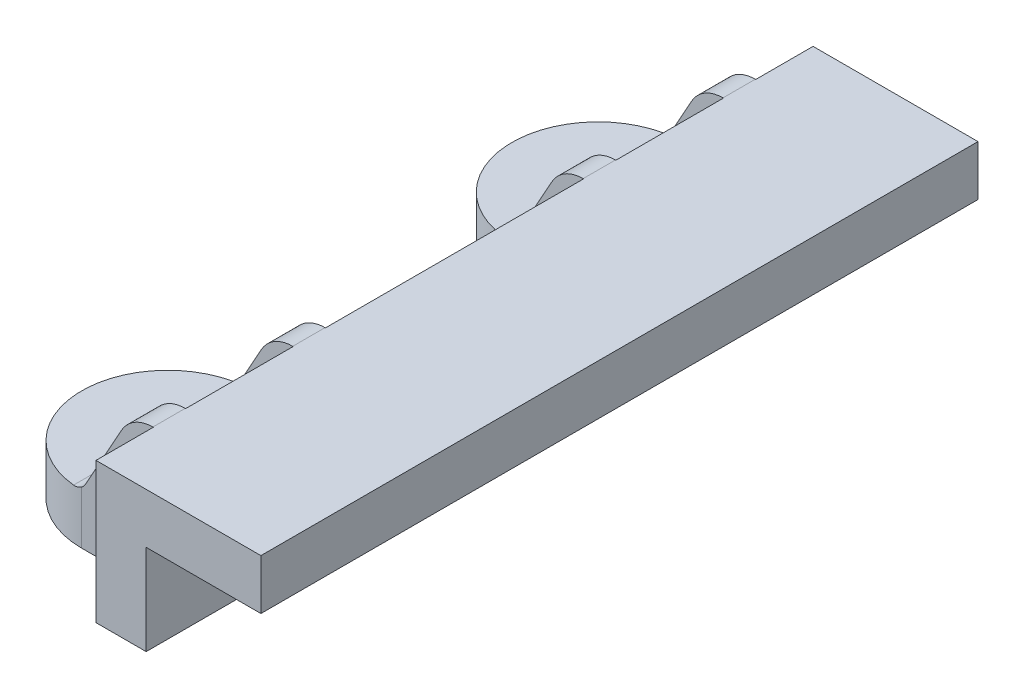
SolidWorks part; units mm, degrees
material "Acrílico (Impacto medio-alto)"
ref_plane "Alzado" through (0, 0, 0) normal (0, 0, 1) x (1, 0, 0)
ref_plane "Planta" through (0, 0, 0) normal (0, 1, 0) x (1, 0, 0)
ref_plane "Vista lateral" through (0, 0, 0) normal (1, 0, 0) x (0, 0, -1)
sketch "Croquis1" plane through (0, 0, 0) normal (0, 0, 1) x (1, 0, 0)
  line L0 (0, 0) -> (0, 9.8)
  line L1 (0, 9.8) -> (11.5, 9.8)
  line L2 (11.5, 9.8) -> (11.5, 6.3)
  line L3 (11.5, 6.3) -> (3.5, 6.3)
  line L4 (3.5, 6.3) -> (3.5, 0)
  line L5 (3.5, 0) -> (0, 0)
  dimension "D1" = 3.5
  dimension "D2" = 8
  dimension "D3" = 3.5
  dimension "D4" = 6.3
extrude "Saliente-Extruir1" add sketch "Croquis1" along normal mid plane 50
sketch "Croquis2" plane through (0, 0, 0) normal (0, 1, 0) x (1, 0, 0)
  line L0 (0, -25) -> (0, 25) construction
  line L1 (0, 9) -> (-5, 9)
  line L2 (0, 9) -> (0, 21)
  line L3 (0, 21) -> (-5, 21)
  line L6 (11.5, 25) -> (0, 25) construction
  arc A0 (-5, 21) -> (-5, 9) centre (-5, 15) ccw
  circle A2 centre (-4.75, 15) radius 2.25
  dimension "D4" = 4.5
  dimension "D1" = 10
  dimension "D2" = 12
  dimension "D3" = 5
  dimension "D5" = 4.75
extrude "Saliente-Extruir2" add sketch "Croquis2" along normal blind 3.5
sketch "Croquis3" plane through (0, 0, -9) normal (0, 0, 1) x (1, 0, 0)
  line L1 (0, 9.8) -> (0, 3.5)
  line L2 (0, 9.8) -> (0, 0) construction
  line L3 (-5, 3.5) -> (0, 3.5) construction
  line L4 (0, 3.5) -> (-5, 3.5)
  line L5 (-5, 3.5) -> (-1.5, 9.8)
  line L6 (-1.5, 9.8) -> (0, 9.8)
  dimension "D1" = 1.5
extrude "Saliente-Extruir3" add sketch "Croquis3" against normal blind 2.25
fillet "Redondeo3" radius 1 1 edges at (-5, 3.5, -10.125)
fillet "Redondeo5" radius 2.5 1 edges at (-1.5, 9.8, -10.125)
ref_plane "Plano1" through (0, 0, -15) normal (0, 0, -1) x (-1, 0, 0)
mirror "Simetría1" about plane through (0, 0, -15) normal (0, 0, -1) of "Saliente-Extruir3", "Redondeo3", "Redondeo5"
mirror "Simetría4" about plane through (0, 0, 0) normal (0, 0, 1) of "Saliente-Extruir2", "Saliente-Extruir3", "Redondeo3", "Redondeo5"
ref_plane "Plano2" through (0, 0, 15) normal (0, 0, -1) x (-1, 0, 0)
sketch "Croquis4" plane through (0, 0, 21) normal (0, 0, 1) x (1, 0, 0)
  line L0 (0, 3.5) -> (-5, 3.5)
  line L1 (-5, 3.5) -> (-1.5, 9.8)
  line L2 (0, 9.8) -> (-1.5, 9.8)
  line L4 (0, 3.5) -> (0, 9.8)
  dimension "D1" = 1.5
extrude "Saliente-Extruir4" add sketch "Croquis4" against normal blind 2.25
fillet "Redondeo6" radius 2.5 1 edges at (-1.5, 9.8, 19.875)
fillet "Redondeo7" radius 1 1 edges at (-5, 3.5, 19.875)
